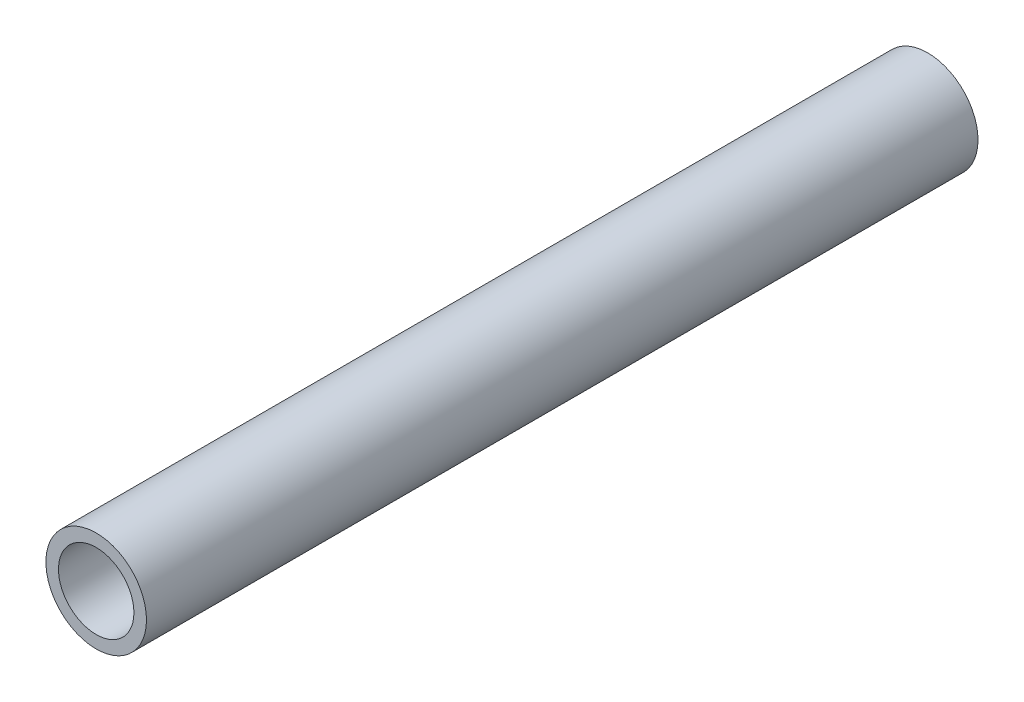
SolidWorks part; units mm, degrees
ref_plane "Front Plane" through (0, 0, 0) normal (0, 0, 1) x (1, 0, 0)
ref_plane "Top Plane" through (0, 0, 0) normal (0, 1, 0) x (1, 0, 0)
ref_plane "Right Plane" through (0, 0, 0) normal (1, 0, 0) x (0, 0, -1)
sketch "Sketch1" plane through (0, 0, 0) normal (0, 0, 1) x (1, 0, 0)
  circle A0 centre (0, 0) radius 19.05
  circle A1 centre (0, 0) radius 25.4
  dimension "D1" = 50.8
  dimension "D2" = 6.35
extrude "Boss-Extrude1" add sketch "Sketch1" along normal blind 420
